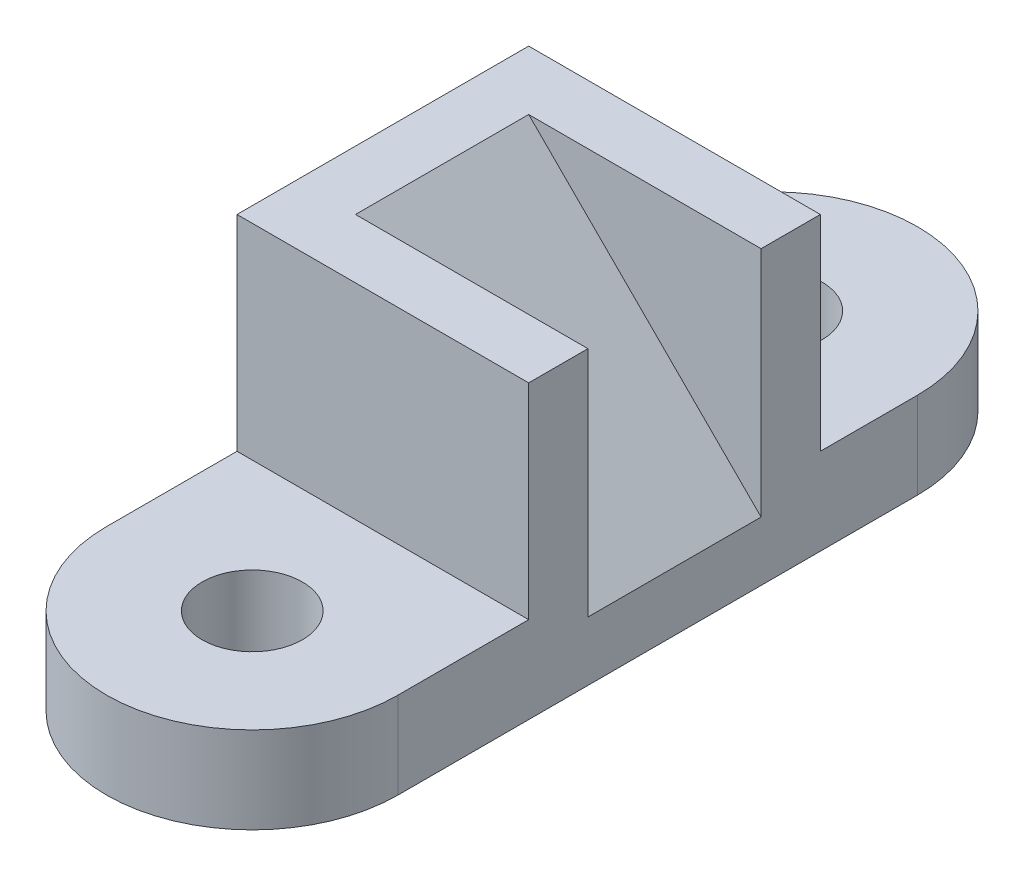
SolidWorks part; units mm, degrees
ref_plane "Front Plane" through (0, 0, 0) normal (0, 0, 1) x (1, 0, 0)
ref_plane "Top Plane" through (0, 0, 0) normal (0, 1, 0) x (1, 0, 0)
ref_plane "Right Plane" through (0, 0, 0) normal (1, 0, 0) x (0, 0, -1)
sketch "Sketch2" plane through (0, 0, 0) normal (0, 1, 0) x (1, 0, 0)
  line L0 (-322.1801, 566.6084) -> (-322.1801, -573.3916)
  line L7 (-192.1801, 223.2058) -> (317.8199, 223.2058)
  line L14 (-192.1801, 223.2058) -> (-192.1801, -156.7942)
  line L15 (317.8199, -286.7942) -> (-322.1801, -286.7942)
  line L17 (317.8199, -156.7942) -> (-192.1801, -156.7942)
  line L19 (-322.1801, 353.2058) -> (317.8199, 353.2058)
  line L22 (317.8199, 566.6084) -> (317.8199, -573.3916)
  circle A0 centre (-2.1801, 566.6084) radius 110
  arc A1 (-322.1801, 566.6084) -> (317.8199, 566.6084) centre (-2.1801, 566.6084) cw
  circle A2 centre (-2.1801, -573.3916) radius 110
  arc A3 (317.8199, -573.3916) -> (-322.1801, -573.3916) centre (-2.1801, -573.3916) cw
  dimension "D2" = 320
  dimension "D1" = 220
  dimension "D4" = 1140
  dimension "D5" = 380
  dimension "D6" = 640
  dimension "D7" = 130
  dimension "D8" = 130
  dimension "D9" = 130
  dimension "D3" = 2
extrude "Boss-Extrude8" add sketch "Sketch2" along normal blind 190 contours A3 L22 L15 L0 A2 | A1 L0 L19 L22 A0 region at (-2.1801, 0, -878.277) region at (-2.1801, 0, 295.6122)
extrude "Boss-Extrude9" add sketch "Sketch2<13>" along normal blind 640 contours L22 L19 L0 L15 L17 L14 L7 region at (-2.1801, 0, -344.1548)
sketch "Sketch2<13>" plane through (0, 0, 0) normal (0, 1, 0) x (1, 0, 0) same geometry as "Sketch2"
extrude "Boss-Extrude10" add sketch "Sketch2<14>" along normal blind 130 contours L22 L7 L17 region at (62.8199, 0, -33.2058)
sketch "Sketch2<14>" plane through (0, 0, 0) normal (0, 1, 0) x (1, 0, 0) same geometry as "Sketch2"
sketch "Sketch13" plane through (0, 0, -223.2058) normal (0, 0, 1) x (1, 0, 0)
  line L0 (-192.1801, 640) -> (317.8199, 130)
  line L8 (-192.1801, 130) -> (317.8199, 130)
  line L9 (317.8199, 130) -> (317.8199, 640)
  line L10 (317.8199, 640) -> (-192.1801, 640)
  line L11 (-192.1801, 640) -> (-192.1801, 130)
  line L14 (-192.1801, 130) -> (317.8199, 130)
  line L17 (-192.1801, 640) -> (-192.1801, 130)
  dimension "D1" = 0
extrude "Boss-Extrude11" add sketch "Sketch13" along normal up to next
equation "\"D8@Sketch2\"=\"D7@Sketch2\""
